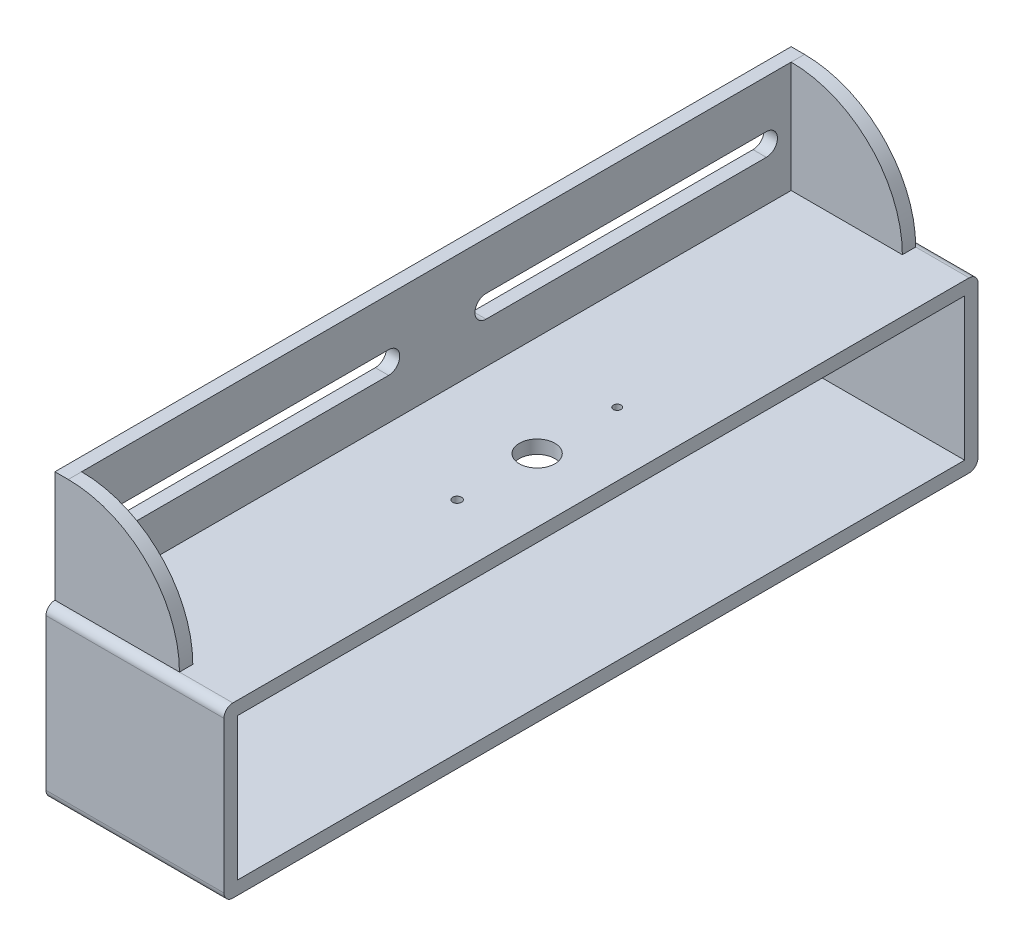
SolidWorks part; units mm, degrees
ref_plane "Front Plane" through (0, 0, 0) normal (0, 0, 1) x (1, 0, 0)
ref_plane "Top Plane" through (0, 0, 0) normal (0, 1, 0) x (1, 0, 0)
ref_plane "Right Plane" through (0, 0, 0) normal (1, 0, 0) x (0, 0, -1)
sketch "Sketch1" plane through (0, 0, 0) normal (1, 0, 0) x (0, 0, -1)
  line L1 (0, 0) -> (169.5, 0)
  line L2 (0, 0) -> (0, 38)
  line L3 (0, 38) -> (169.5, 38)
  line L4 (169.5, 0) -> (169.5, 38)
extrude "Boss-Extrude1" add sketch "Sketch1" along normal blind 3 contours L3 L4 L1 L2
ref_plane "Plane1" through (0, 0, -169.5) normal (0, 1, 0) x (1, 0, 0)
sketch "Sketch12" plane through (0, 0, -169.5) normal (0, 1, 0) x (1, 0, 0)
  line L1 (0, 0) -> (40, 0)
  line L2 (0, 0) -> (0, -3)
  line L3 (0, -3) -> (40, -3)
  line L4 (40, 0) -> (40, -3)
extrude "Boss-Extrude3" add sketch "Sketch12" along normal blind 38 contours L1 L4 L3 L2
ref_plane "Plane2" through (3, 0, 0) normal (0, 1, 0) x (1, 0, 0)
sketch "Sketch16" plane through (3, 0, 0) normal (0, 1, 0) x (1, 0, 0)
  line L1 (0, 0) -> (37, 0)
  line L2 (0, 0) -> (0, 3)
  line L3 (0, 3) -> (37, 3)
  line L4 (37, 0) -> (37, 3)
extrude "Boss-Extrude4" add sketch "Sketch16" along normal up to vertex (38 mm away) contours L3 L4 L1 L2 up to point (3, 38, 0)
sketch "Sketch18" plane through (0, 38, 0) normal (0, 1, 0) x (1, 0, 0)
  line L1 (40, 166.5) -> (3, 166.5)
  line L2 (40, 166.5) -> (40, 3)
  line L3 (40, 3) -> (3, 3)
  line L4 (3, 166.5) -> (3, 3)
extrude "Boss-Extrude5" add sketch "Sketch18" against normal blind 3 contours L2 L3 L4 L1
sketch "Sketch19" plane through (0, 0, 0) normal (0, -1, 0) x (-1, 0, 0)
  line L1 (-40, 3) -> (-3, 3)
  line L2 (-40, 3) -> (-40, 166.5)
  line L3 (-40, 166.5) -> (-3, 166.5)
  line L4 (-3, 3) -> (-3, 166.5)
fillet "Fillet1" radius 2 1 edges at (20, 0, 0)
fillet "Fillet2" radius 2 1 edges at (20, 38, 0)
fillet "Fillet3" radius 2 1 edges at (20, 38, -169.5)
fillet "Fillet4" radius 2 1 edges at (20, 0, -169.5)
sketch "Sketch37" plane through (0, 0, 0) normal (-1, 0, 0) x (0, 0, 1)
  line L1 (-167.5, 38) -> (-2, 38)
  line L2 (-167.5, 38) -> (-167.5, 63)
  line L3 (-167.5, 63) -> (-2, 63)
  line L4 (-2, 38) -> (-2, 63)
extrude "Boss-Extrude12" add sketch "Sketch37" against normal blind 3 contours L3 L4 L1 L2
sketch "Sketch40" plane through (0, 0, -167.5) normal (0, 0, -1) x (-1, 0, 0)
  line L0 (-40, 38) -> (-3, 38) construction
  line L1 (-3, 63) -> (-28, 63)
  line L2 (-3, 63) -> (-3, 38)
  line L3 (-3, 38) -> (-28, 38)
  line L4 (-28, 63) -> (-28, 38)
extrude "Boss-Extrude13" add sketch "Sketch40" against normal blind 3 contours L1 L4 L3 L2
fillet "Fillet11" radius 25 1 edges at (28, 63, -166)
sketch "Sketch41" plane through (0, 0, -2) normal (0, 0, 1) x (1, 0, 0)
  line L1 (3, 63) -> (28, 63)
  line L2 (3, 63) -> (3, 38)
  line L3 (3, 38) -> (28, 38)
  line L4 (28, 63) -> (28, 38)
extrude "Boss-Extrude14" add sketch "Sketch41" against normal blind 3
fillet "Fillet12" radius 25 1 edges at (28, 63, -3.5)
sketch "Sketch57" plane through (3, 0, 0) normal (1, 0, 0) x (0, 0, -1)
  line L0 (11.0186, 49.7493) -> (74.0186, 49.7493) construction
  line L1 (11.0186, 52.2493) -> (74.0186, 52.2493)
  line L2 (11.0186, 47.2493) -> (74.0186, 47.2493)
  line L3 (158.9189, 49.7493) -> (95.9189, 49.7493) construction
  line L4 (158.9189, 47.2493) -> (95.9189, 47.2493)
  line L5 (158.9189, 52.2493) -> (95.9189, 52.2493)
  arc A0 (11.0186, 52.2493) -> (11.0186, 47.2493) centre (11.0186, 49.7493) ccw
  arc A1 (74.0186, 47.2493) -> (74.0186, 52.2493) centre (74.0186, 49.7493) ccw
  arc A2 (158.9189, 47.2493) -> (158.9189, 52.2493) centre (158.9189, 49.7493) ccw
  arc A3 (95.9189, 52.2493) -> (95.9189, 47.2493) centre (95.9189, 49.7493) ccw
  point P2 (42.5186, 49.7493)
  point P9 (127.4189, 49.7493)
sketch "Sketch62" plane through (0, 38, 0) normal (0, 1, 0) x (1, 0, 0)
  circle A0 centre (25.6495, 84.75) radius 4
  circle A1 centre (25.6495, 102.75) radius 1
  point P4 (0, 0)
sketch "Sketch63" plane through (0, 38, 0) normal (0, 1, 0) x (1, 0, 0)
  circle A0 centre (25.6495, 66.75) radius 1
sketch "Sketch66" plane through (0, 38, 0) normal (0, 1, 0) x (1, 0, 0)
  circle A0 centre (25.6495, 102.75) radius 0.875
sketch "Sketch67" plane through (0, 0, 0) normal (-1, 0, 0) x (0, 0, 1)
  circle A0 centre (-84.75, 20.281) radius 12
extrude "Cut-Extrude19" cut sketch "Sketch57" against normal blind 10
extrude "Cut-Extrude23" cut sketch "Sketch62" against normal blind 10 contours A0
extrude "Cut-Extrude24" cut sketch "Sketch66" against normal blind 10 contours A0
extrude "Cut-Extrude26" cut sketch "Sketch63" against normal blind 10 contours A0
extrude "Boss-Extrude16" add sketch "Sketch19" against normal blind 3 contours L2 L3 L4 L1
sketch "Sketch118" plane through (0, 0, 0) normal (-1, 0, 0) x (0, 0, 1)
  circle A0 centre (-54.75, 20.281) radius 12
  point P2 (0, 0)
sketch "Sketch123" plane through (0, 0, 0) normal (-1, 0, 0) x (0, 0, 1)
  circle A0 centre (-114.75, 20.281) radius 13
  circle A1 centre (-144.75, 20.281) radius 13.0614
sketch "Sketch125" plane through (0, 0, 0) normal (-1, 0, 0) x (0, 0, 1)
  circle A0 centre (-24.75, 20.281) radius 13
extrude "Cut-Extrude30" cut sketch "Sketch123" against normal blind 3 contours A1
extrude "Cut-Extrude31" cut sketch "Sketch125" against normal blind 3 contours A0
sketch "Sketch126" plane through (0, 0, 0) normal (-1, 0, 0) x (0, 0, 1)
  circle A0 centre (-114.75, 20.281) radius 13
extrude "Cut-Extrude32" cut sketch "Sketch126" against normal blind 3 contours A0
extrude "Cut-Extrude33" cut sketch "Sketch67" against normal blind 3 contours A0
extrude "Cut-Extrude34" cut sketch "Sketch118" against normal blind 3 contours A0
